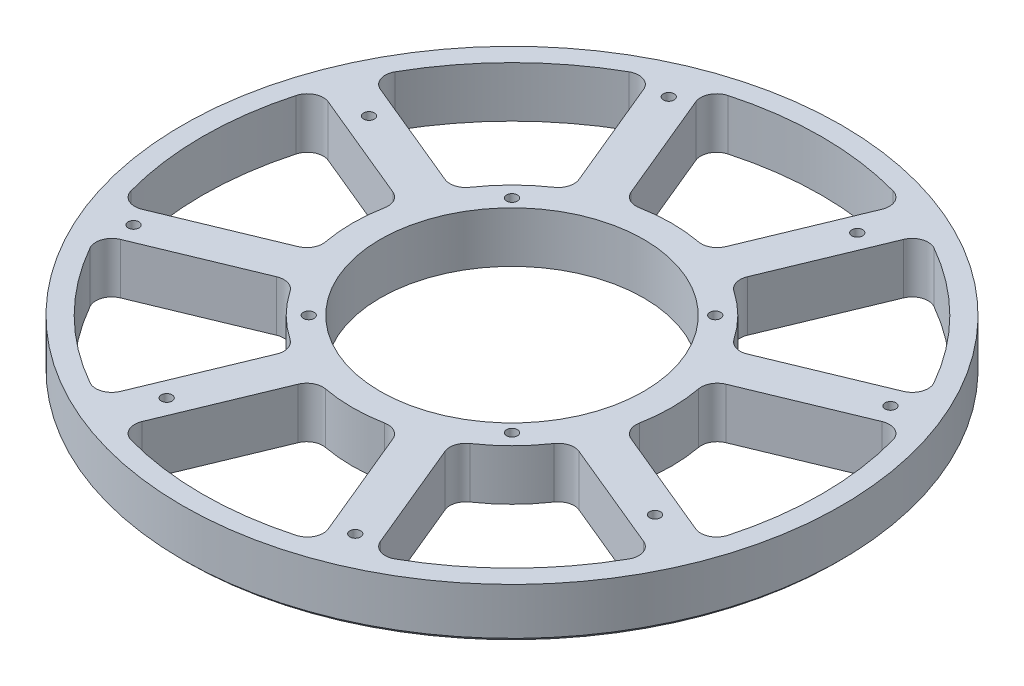
SolidWorks part; units mm, degrees
material "6061-T6 (SS)"
ref_plane "Front Plane" through (0, 0, 0) normal (0, 0, 1) x (1, 0, 0)
ref_plane "Top Plane" through (0, 0, 0) normal (0, 1, 0) x (1, 0, 0)
ref_plane "Right Plane" through (0, 0, 0) normal (1, 0, 0) x (0, 0, -1)
sketch "Sketch2" plane through (0, 0, 0) normal (1, 0, 0) x (0, 0, -1)
  line L0 (0, 0) -> (-82.55, 0)
  line L1 (-82.55, 0) -> (-82.55, 12.7)
  line L2 (-82.55, 12.7) -> (0, 12.7)
  line L5 (0, 12.7) -> (0, 0)
  dimension "D1" = 82.55
  dimension "D2" = 12.7
ref_axis "Axis1" through (0, -0.5, 0) along (0, 1, 0)
revolve "Revolve1" add sketch "Sketch2" angle 360 about axis through (0, -0.5, 0) along (0, 1, 0)
hole_wizard "#6-32 Tapped Hole1" positions "Sketch6" profile "Sketch7" tap size "#6-32" standard "ANSI Inch" end condition through all
sketch "Sketch6" plane through (0, 12.7, 0) normal (0, 1, 0) x (1, 0, 0)
  line L0 (0, 0) -> (-53.438, 129.0108) construction
  line L2 (0, 0) -> (0, 109.0908) construction
  line L3 (0, 0) -> (-76.2663, 31.5905) construction
  line L4 (0, 0) -> (-68.4315, 68.4315) construction
  circle A0 centre (0, 0) radius 82.55 construction
  point P0 (-27.7637, 67.0275)
  point P18 (-61.1608, 25.3336)
  point P27 (-25.4558, 25.4558)
  dimension "D1" = 22.5
  dimension "D2" = 72.55
  dimension "D3" = 45
  dimension "D4" = 66.2
  dimension "D6" = 22.5
  dimension "D5" = 36
sketch "Sketch7" plane through (-27.7637, 12.7, -67.0275) normal (1, 0, 0) x (0, 0, 1)
  line L0 (0, 0) -> (0, 12.7)
  line L1 (0, 12.7) -> (1.3525, 12.7)
  line L2 (1.3525, 12.7) -> (1.3525, 0)
  line L5 (1.3525, 0) -> (0, 0)
  line L11 (0, -6.35) -> (0, 107.95) construction
  dimension "Thread Major Dia." = 2.7051
  dimension "Thru Tap Drill Depth" = 12.7
pattern_circular "CirPattern3" count 4 over 360 about axis through (0, -0.5, 0) along (0, 1, 0) of "#6-32 Tapped Hole1"
sketch "Sketch8" plane through (0, 12.7, 0) normal (0, 1, 0) x (1, 0, 0)
  line L4 (0, 0) -> (0, 93.9995) construction
  line L5 (0, 0) -> (113.8372, 0) construction
  line L6 (-10.5679, 38.5787) -> (-24.996, 73.4112)
  line L7 (10.5679, 38.5787) -> (24.996, 73.4112)
  line L8 (0, 0) -> (-27.7637, 67.0275) construction
  arc A0 (-10.5679, 38.5787) -> (10.5679, 38.5787) centre (0, 0) cw
  arc A1 (-24.996, 73.4112) -> (24.996, 73.4112) centre (0, 0) cw
  circle A2 centre (0, 0) radius 82.55 construction
  dimension "D1" = 40
  dimension "D2" = 5
  dimension "D3" = 5
extrude "Cut-Extrude1" cut sketch "Sketch8" against normal through all
fillet "Fillet1" radius 4 4 edges at (10.5679, 6.35, -38.5787) (24.996, 6.35, -73.4112) (-10.5679, 6.35, -38.5787) (-24.996, 6.35, -73.4112)
pattern_circular "CirPattern4" count 8 over 360 about axis through (0, -0.5, 0) along (0, 1, 0) of "Cut-Extrude1", "Fillet1"
chamfer "Chamfer2" distance 1 angle 45 1 edges at (0, 0, -82.55)
sketch "Sketch9" plane through (0, 12.7, 0) normal (0, 1, 0) x (1, 0, 0)
  circle A0 centre (0, 0) radius 33
  dimension "D1" = 66
extrude "Cut-Extrude2" cut sketch "Sketch9" against normal through all
equation "\"TubeDiameter\" = 6.500in"
equation "\"D1@Sketch2\"=\"TubeDiameter\"/2"
equation "\"D2@Sketch6\"=\"TubeDiameter\"/2-10mm"
